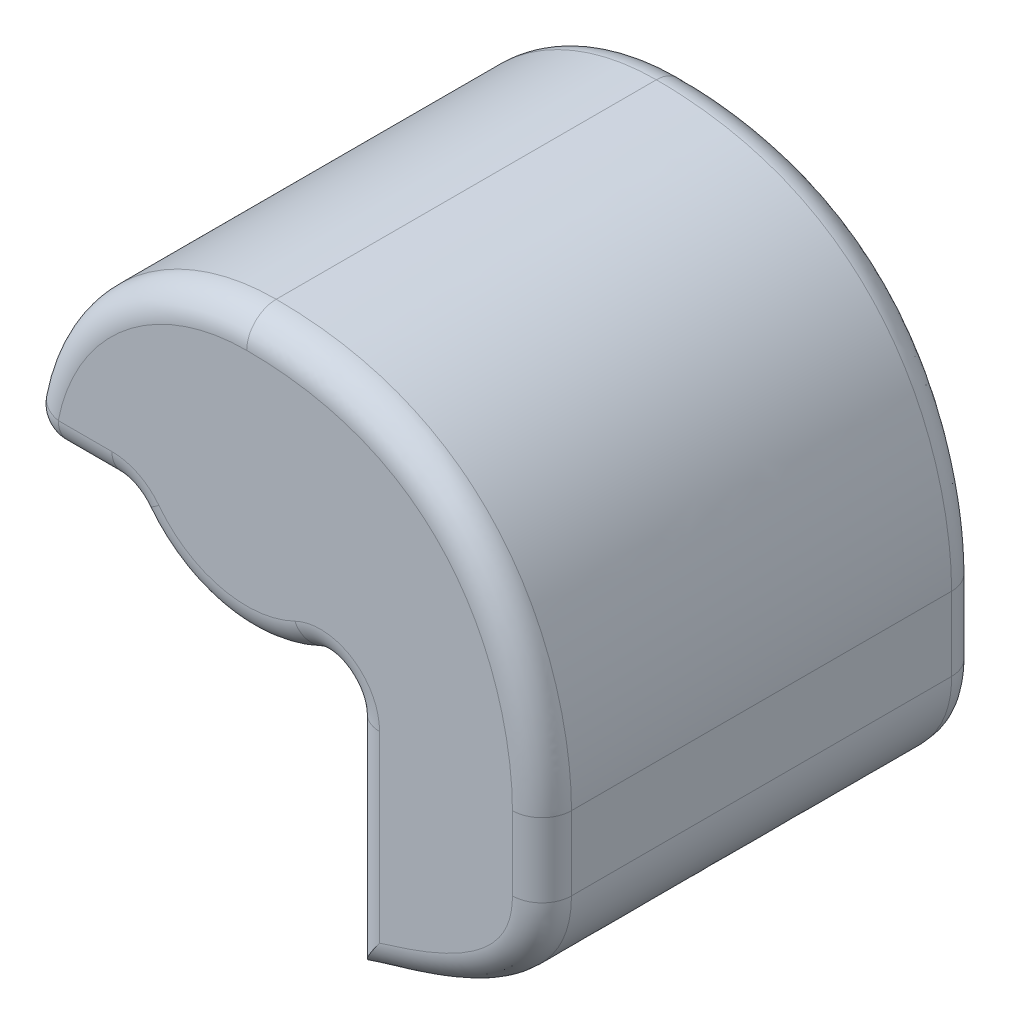
SolidWorks part; units mm, degrees
note: The reader was unsure of these and kept them because the rebuilt part matched: shared geometry of "Sketch1<3>".
ref_plane "Front Plane" through (0, 0, 0) normal (0, 0, 1) x (1, 0, 0)
ref_plane "Top Plane" through (0, 0, 0) normal (0, 1, 0) x (1, 0, 0)
ref_plane "Right Plane" through (0, 0, 0) normal (1, 0, 0) x (0, 0, -1)
sketch "Sketch1" plane through (0, 0, 0) normal (0, 0, 1) x (1, 0, 0)
  line L0 (-15, -5) -> (-8.0777, -5)
  line L1 (7, -6.4226) -> (7, -15.5)
  line L2 (7, -15.5) -> (20, -15.5) construction
  line L4 (20, -15.5) -> (20, -10.5)
  line L5 (20, 7.5498) -> (20, -22.5085) construction
  line L6 (-13.4863, 9.5) -> (13.4863, 9.5) construction
  line L7 (7, -15.5) -> (7, -25.5)
  line L8 (20, -6.8173) -> (20, -24.1827) construction
  circle A0 centre (0, 0) radius 2
  circle A1 centre (0, 0) radius 9.5 construction
  arc A2 (-8.0777, -5) -> (7, -6.4226) centre (0, 0) ccw
  arc A4 (-15, -5) -> (0, 9.5) centre (0, -5.5086) cw
  spline S0 degree 3 poles (20, -10.5) (20, -3.4711) (16.2995, 9.5) (0, 9.5) knots 0 0 0 0 1 1 1 1
  spline S1 degree 3 poles (7, -25.5) (10.5423, -24.1965) (20, -22.6469) (20, -15.5) knots 0 0 0 0 1 1 1 1
  point P21 (20, -13)
  dimension "D1" = 4
  dimension "D2" = 19
  dimension "D6" = 10
  dimension "D3" = 5
  dimension "D4" = 7
  dimension "D5" = 15
  dimension "D7" = 13
  dimension "D8" = 20
  dimension "D9" = 5
extrude "Boss-Extrude1" add sketch "Sketch1" along normal blind 8.25 contours A0 | L7 S1 L4 S0 A4 L0 A2 L1 A0
fillet "Fillet1" radius 2 3 edges at (7, -6.4226, 4.125) (-8.0777, -5, 4.125) (-15, -5, 4.125)
extrude "Boss-Extrude2" add sketch "Sketch1<3>" against normal blind 13.25 contours A0
sketch "Sketch1<3>" plane through (0, 0, 0) normal (0, 0, 1) x (1, 0, 0) same geometry as "Sketch1"
ref_plane "Plane1" through (0, 0, -6.625) normal (0, 0, -1) x (-1, 0, 0)
mirror "Mirror1" about plane through (0, 0, -6.625) normal (0, 0, -1) of "Fillet1", "Boss-Extrude1"
sketch "Sketch2" plane through (0, 0, 0) normal (0, 0, -1) x (-1, 0, 0)
  line L0 (-7, -10.3562) -> (-7, -6.4226)
  line L1 (9.1241, -3) -> (12.7644, -3)
  line L2 (-18, -10.5) -> (-18, -15.5)
  line L3 (-7, -25.5) -> (-7, -10.3562)
  line L4 (9.1241, -5) -> (12.7644, -5)
  line L5 (-20, -10.5) -> (-20, -15.5)
  line L6 (-7, -25.5) -> (-7, -10.3562)
  line L7 (9.1241, -5) -> (12.7644, -5)
  line L8 (-20, -10.5) -> (-20, -15.5)
  line L9 (-9, -22.7718) -> (-9, -10.3562)
  line L10 (9.3234, 3.5632) -> (10.7569, 4.9579)
  circle A0 centre (0, 0) radius 9.5 construction
  circle A1 centre (0, 0) radius 9.5
  arc A2 (-3.2609, -6.754) -> (-9, -10.3562) centre (-5, -10.3562) ccw
  arc A3 (-3.2609, -6.754) -> (5.9505, -4.5652) centre (0, 0) ccw
  arc A4 (9.1241, -3) -> (5.9505, -4.5652) centre (9.1241, -7) ccw
  arc A5 (12.7644, -3) -> (12.7644, -3) centre (12.7644, -3) ccw
  arc A6 (12.7644, -3) -> (0, 7.5) centre (0, -5.5086) ccw
  arc A7 (-4.1304, -8.5551) -> (-7, -10.3562) centre (-5, -10.3562) ccw
  arc A8 (-4.1304, -8.5551) -> (-7, -10.3562) centre (-5, -10.3562) ccw
  arc A9 (9.1241, -5) -> (7.5373, -5.7826) centre (9.1241, -7) ccw
  arc A10 (-4.1304, -8.5551) -> (7.5373, -5.7826) centre (0, 0) ccw
  arc A11 (9.1241, -5) -> (7.5373, -5.7826) centre (9.1241, -7) ccw
  arc A12 (12.7644, -5) -> (14.7269, -2.6143) centre (12.7644, -3) ccw
  arc A13 (14.7269, -2.6143) -> (0, 9.5) centre (0, -5.5086) ccw
  arc A16 (-4.1304, -8.5551) -> (7.5373, -5.7826) centre (0, 0) ccw
  arc A19 (14.7269, -2.6143) -> (0, 9.5) centre (0, -5.5086) ccw
  arc A20 (12.7644, -5) -> (14.7269, -2.6143) centre (12.7644, -3) ccw
  spline S0 degree 1 poles (0, 7.5) (-18, -10.5) knots 0 0 1 1 construction
  spline S1 degree 1 poles (-18, -15.5) (-9, -22.7718) knots 0 0 1 1 construction
  spline S2 degree 3 poles (1787.3039, 838.0788) (-1966.5143, -741.8836) (1981.8382, 591.5205) (-1928.9464, -578.2796) knots -4.354479 -4.354479 -4.354479 -4.354479 5.686185 5.686185 5.686185 5.686185 only from (-20, -15.5) to (-7, -25.5)
  spline S3 degree 3 poles (1211.4295, -1577.1658) (-999.3169, 1836.0114) (737.0887, -1963.4046) (-581.7509, 1907.8325) knots -3.788257 -3.788257 -3.788257 -3.788257 5.444032 5.444032 5.444032 5.444032 only from (0, 9.5) to (-20, -10.5)
  spline S4 degree 3 poles (-20, -15.5) (-20, -22.6469) (-10.5423, -24.1965) (-7, -25.5) knots 0 0 0 0 1 1 1 1
  spline S5 degree 3 poles (0, 9.5) (-16.2995, 9.5) (-20, -3.4711) (-20, -10.5) knots 0 0 0 0 1 1 1 1
  spline S6 degree 3 poles (0, 7.5) (-0.4633, 7.5) (-1.4081, 7.4763) (-3.1486, 7.3398) (-5.1536, 7.0127) (-7.2744, 6.4022) (-9.7644, 5.3371) (-12.301, 3.5999) (-14.5958, 1.0249) (-16.2458, -1.8887) (-17.142, -4.4391) (-17.6083, -6.4406) (-17.843, -7.8932) (-17.9521, -9.0345) (-17.9935, -9.8973) (-18, -10.2964) (-18, -10.5) knots 0 0 0 0 0.03125 0.0625 0.125 0.1875 0.25 0.375 0.5 0.625 0.75 0.8125 0.875 0.9375 0.96875 1 1 1 1
  spline S7 degree 3 poles (-18, -15.5) (-18, -15.7558) (-17.9638, -16.2875) (-17.7696, -17.1765) (-17.3267, -18.1507) (-16.4736, -19.1942) (-14.9056, -20.459) (-12.8241, -21.4812) (-10.5974, -22.2785) (-9.539, -22.608) (-9, -22.7718) knots 0 0 0 0 0.050516 0.101032 0.202065 0.303097 0.404129 0.606194 0.707226 0.808258 0.808258 0.808258 0.808258
  dimension "D2" = 2
  dimension "D1" = 0
extrude "Boss-Extrude3" add sketch "Sketch2" along normal up to surface (13.25 mm away)
sketch "Sketch3" plane through (20, 0, 0) normal (1, 0, 0) x (0, 0, -1)
  line L0 (-8.25, -10.5) -> (21.5, -10.5) construction
  line L1 (21.5, -15.5) -> (21.5, -10.5) construction
  point P0 (6.625, -13)
  point P1 (6.625, -10.5)
  point P2 (21.5, -13)
fillet "Fillet5" radius 4 2 edges at (7, -6.4226, -6.625) (6.962, 6.4638, -6.625)
fillet "Fillet6" radius 2 20 edges at (20, -13, 8.25) (-10.9443, -5, 8.25) (-9.5347, 6.0823, 8.25) (7, -17.9281, 8.25) (-2.1962, -9.2427, 8.25) (-14.309, -4.2706, 8.25) (6.0632, -8.6622, 8.25) (-8.2395, -5.2063, 8.25) (20, -13, -21.5) (-9.5347, 6.0823, -21.5) (-10.9443, -5, -21.5) (7, -17.9281, -21.5) (-2.1962, -9.2427, -21.5) (-14.309, -4.2706, -21.5) (6.0632, -8.6622, -21.5) (-8.2395, -5.2063, -21.5)
